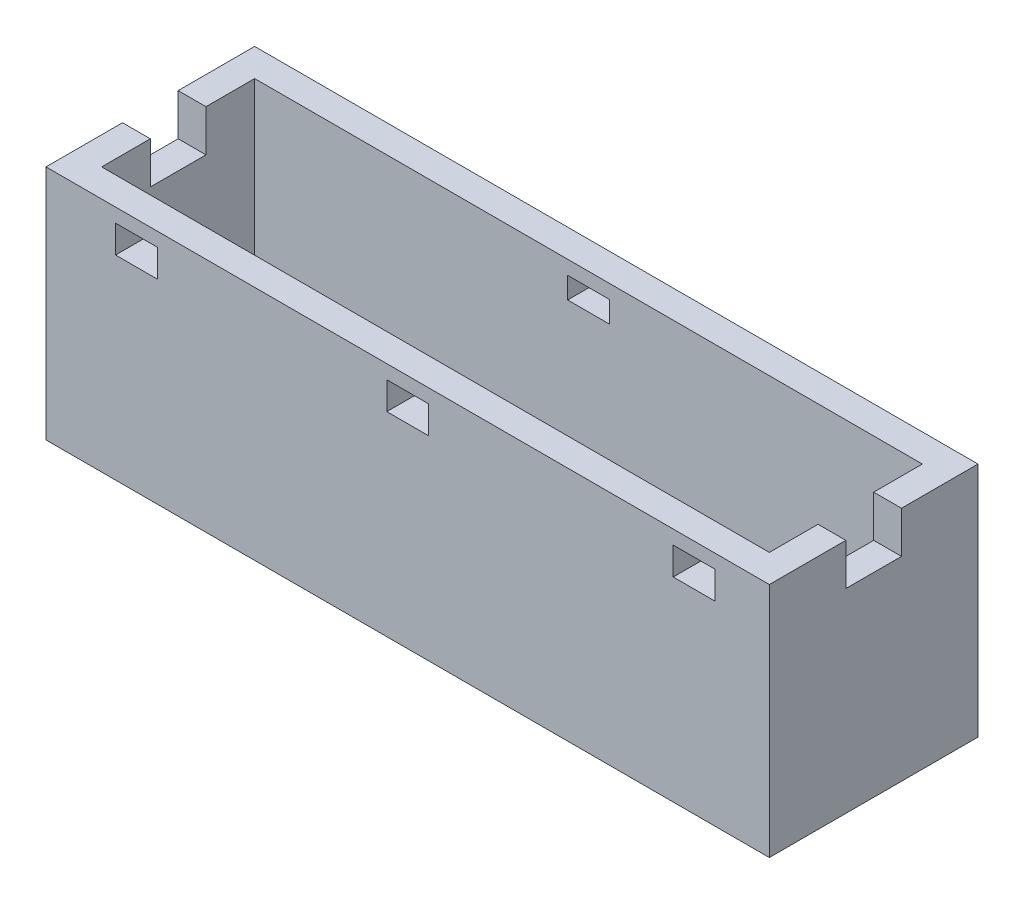
SolidWorks part; units mm, degrees
ref_plane "前基準面" through (0, 0, 0) normal (0, 0, 1) x (1, 0, 0)
ref_plane "上基準面" through (0, 0, 0) normal (0, 1, 0) x (1, 0, 0)
ref_plane "右基準面" through (0, 0, 0) normal (1, 0, 0) x (0, 0, -1)
sketch "草圖1" plane through (0, 0, 0) normal (0, 1, 0) x (1, 0, 0)
  line L1 (-260, 75) -> (260, 75)
  line L2 (-260, 75) -> (-260, -75)
  line L3 (-260, -75) -> (260, -75)
  line L4 (260, 75) -> (260, -75)
  line L5 (-260, 75) -> (260, -75) construction
  line L6 (-260, -75) -> (260, 75) construction
  point P0 (0, 0)
  dimension "D1" = 520
  dimension "D2" = 150
extrude "填料-伸長1" add sketch "草圖1" along normal blind 140
sketch "草圖2" plane through (0, 140, 0) normal (0, 1, 0) x (1, 0, 0)
  line L0 (260, 75) -> (-260, 75) construction
  line L1 (-240, 55) -> (240, 55)
  line L2 (-240, 55) -> (-240, -55)
  line L3 (-240, -55) -> (240, -55)
  line L4 (240, 55) -> (240, -55)
  line L5 (-240, 55) -> (240, -55) construction
  line L6 (-240, -55) -> (240, 55) construction
  line L7 (-260, 75) -> (-260, -75) construction
  point P0 (0, 0)
  dimension "D1" = 20
  dimension "D2" = 20
extrude "除料-伸長1" cut sketch "草圖2" against normal blind 120
ref_plane "平面1" through (0, 0, 80) normal (0, 0, 1) x (1, 0, 0)
sketch "草圖11" plane through (-260, 0, 0) normal (-1, 0, 0) x (0, 0, 1)
  line L0 (-75, 140) -> (75, 140) construction
  line L1 (-20, 140) -> (20, 140)
  line L2 (-20, 140) -> (-20, 110)
  line L3 (-20, 110) -> (20, 110)
  line L4 (20, 140) -> (20, 110)
  line L5 (-75, 140) -> (-75, 0) construction
  dimension "D1" = 40
  dimension "D2" = 30
  dimension "D3" = 55
extrude "除料-伸長3" cut sketch "草圖11" against normal through all
sketch "草圖13" plane through (0, 0, 0) normal (0, -1, 0) x (1, 0, 0)
  line L1 (-260, -75) -> (260, -75)
  line L2 (-260, -75) -> (-260, 75)
  line L3 (-260, 75) -> (260, 75)
  line L4 (260, -75) -> (260, 75)
extrude "填料-伸長6" add sketch "草圖13" along normal blind 30
sketch "草圖18" plane through (0, 0, -75) normal (0, 0, -1) x (-1, 0, 0)
  line L0 (-260, 140) -> (-260, -30) construction
  line L1 (-15, 130) -> (15, 130)
  line L2 (-15, 130) -> (-15, 114.647)
  line L3 (-15, 114.647) -> (15, 114.647)
  line L4 (15, 130) -> (15, 114.647)
  line L5 (-15, 130) -> (15, 114.647) construction
  line L6 (-15, 114.647) -> (15, 130) construction
  line L7 (260, 140) -> (260, -30) construction
  line L8 (-260, 140) -> (260, 140) construction
  point P0 (0, 122.3235)
  dimension "D1" = 245
  dimension "D2" = 245
  dimension "D3" = 10
extrude "除料-伸長8" cut sketch "草圖18" against normal blind 30
fillet "圓角1" radius 10 1 edges at (0, 130, -75)
sketch "草圖21" plane through (0, 0, 75) normal (0, 0, 1) x (1, 0, 0)
  line L0 (-260, 140) -> (-260, -30) construction
  line L1 (-210, 130) -> (-180, 130)
  line L2 (-210, 130) -> (-210, 110.1244)
  line L3 (-210, 110.1244) -> (-180, 110.1244)
  line L4 (-180, 130) -> (-180, 110.1244)
  line L5 (-210, 130) -> (-180, 110.1244) construction
  line L6 (-210, 110.1244) -> (-180, 130) construction
  line L7 (-260, 140) -> (260, 140) construction
  point P0 (-195, 120.0622)
  dimension "D1" = 50
  dimension "D2" = 10
  dimension "D3" = 30
extrude "除料-伸長9" cut sketch "草圖21" against normal blind 30
sketch "草圖22" plane through (0, 0, 75) normal (0, 0, 1) x (1, 0, 0)
  line L0 (0, -1000) -> (0, 49000) construction
  line L2 (-260, 140) -> (260, 140) construction
  line L3 (-15, 130) -> (15, 130)
  line L4 (-15, 130) -> (-15, 110.12)
  line L5 (-15, 110.12) -> (15, 110.12)
  line L6 (15, 130) -> (15, 110.12)
  line L7 (-15, 130) -> (15, 110.12) construction
  line L8 (-15, 110.12) -> (15, 130) construction
  point P5 (0, 120.06)
  dimension "D1" = 10
  dimension "D2" = 30
  dimension "D3" = 19.88
extrude "除料-伸長10" cut sketch "草圖22" against normal blind 30
sketch "草圖25" plane through (0, 0, 75) normal (0, 0, 1) x (1, 0, 0)
  line L0 (-260, 140) -> (260, 140) construction
  line L1 (190.8911, 130) -> (220.8911, 130)
  line L2 (190.8911, 130) -> (190.8911, 110.12)
  line L3 (190.8911, 110.12) -> (220.8911, 110.12)
  line L4 (220.8911, 130) -> (220.8911, 110.12)
  line L5 (190.8911, 130) -> (220.8911, 110.12) construction
  line L6 (190.8911, 110.12) -> (220.8911, 130) construction
  point P0 (205.8911, 120.06)
  dimension "D1" = 10
  dimension "D2" = 19.88
  dimension "D3" = 30
extrude "除料-伸長12" cut sketch "草圖25" against normal blind 30
